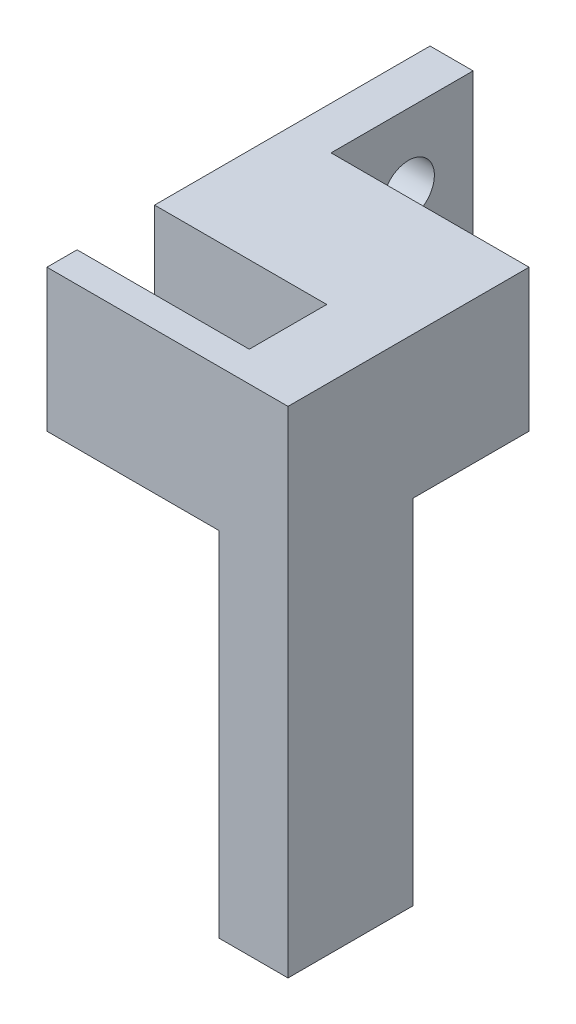
SolidWorks part; units mm, degrees
ref_plane "前视基准面" through (0, 0, 0) normal (0, 0, 1) x (1, 0, 0)
ref_plane "上视基准面" through (0, 0, 0) normal (0, 1, 0) x (1, 0, 0)
ref_plane "右视基准面" through (0, 0, 0) normal (1, 0, 0) x (0, 0, -1)
other "Configuration Table"
sketch "草图1" plane through (0, 0, 0) normal (1, 0, 0) x (0, 0, -1)
  line L5 (0, 0) -> (-2.9, 0)
  line L6 (0, 0) -> (0, -11.5)
  line L7 (0, -11.5) -> (-2.9, -11.5)
  line L8 (-2.9, 0) -> (-2.9, -11.5)
  point P4 (-0.9757, -0.6511)
  dimension "D1" = 2.9
  dimension "D2" = 11.5
extrude "凸台-拉伸1" add sketch "草图1" along normal blind 1.6 contours L7 L8 L5 L6 | L7 L8 L5 L6 region at (0, -5.75, 1.45)
sketch "草图2" plane through (0, 0, 0) normal (-1, 0, 0) x (0, 0, 1)
  line L0 (2.9, 0) -> (2.9, -11.5) construction
  line L1 (2.2, -3.3) -> (2.9, -3.3)
  line L2 (2.2, -3.3) -> (2.2, 0)
  line L3 (2.2, 0) -> (2.9, 0)
  line L4 (2.9, -3.3) -> (2.9, 0)
  line L5 (0, 0) -> (2.9, 0) construction
  line L6 (0, 0) -> (0.4, 0)
  line L7 (0, 0) -> (0, -3.3)
  line L8 (0, -3.3) -> (0.4, -3.3)
  line L9 (0.4, 0) -> (0.4, -3.3)
  point P12 (0, 0)
  dimension "D1" = 3.3
  dimension "D2" = 0.7
  dimension "D3" = 0.4
extrude "凸台-拉伸2" add sketch "草图2" along normal blind 4 contours L4 L3 L2 L1 | L9 L8 L7 L6
sketch "草图3" plane through (0, 0, 0) normal (0, 0, -1) x (-1, 0, 0)
  line L0 (-1.6, 0) -> (4, 0) construction
  line L1 (-1.6, 0) -> (4, 0)
  line L2 (-1.6, 0) -> (-1.6, -3.3)
  line L3 (-1.6, -3.3) -> (4, -3.3)
  line L4 (4, 0) -> (4, -3.3)
  line L5 (4, 0) -> (4, -3.3) construction
  line L6 (-1.6, 0) -> (-1.6, -11.5) construction
  line L7 (4, -3.3) -> (0, -3.3) construction
  point P8 (-0.613, -2.3514)
extrude "凸台-拉伸3" add sketch "草图3" along normal blind 3
sketch "草图4" plane through (0, 0, -3) normal (0, 0, -1) x (-1, 0, 0)
  line L0 (-1.6, -3.3) -> (4, -3.3) construction
  line L1 (3, -3.3) -> (4, -3.3)
  line L2 (3, -3.3) -> (3, 0)
  line L3 (3, 0) -> (4, 0)
  line L4 (4, -3.3) -> (4, 0)
  line L5 (4, -3.3) -> (4, 0) construction
  line L6 (4, 0) -> (-1.6, 0) construction
  dimension "D1" = 1
extrude "凸台-拉伸4" add sketch "草图4" along normal blind 3
sketch "草图5" plane through (-3, 0, 0) normal (1, 0, 0) x (0, 0, -1)
  line L1 (4.5, 0) -> (4.5, -3.3)
  line L2 (6, 0) -> (3, 0) construction
  line L3 (6, -3.3) -> (3, -3.3) construction
  circle A0 centre (4.5, -1.65) radius 0.6
  point P2 (0, 0)
  dimension "D1" = 1.2
extrude "切除-拉伸1" cut sketch "草图5" against normal through all contours A0
sketch "草图6" plane through (0, 0, -3) normal (0, 0, -1) x (-1, 0, 0)
  line L0 (-1.6, -3.3) -> (3, -3.3) construction
  line L1 (-1.6, -3.3) -> (3, -3.3)
  line L2 (-1.6, -3.3) -> (-1.6, 0)
  line L3 (-1.6, 0) -> (3, 0)
  line L4 (3, -3.3) -> (3, 0)
  line L5 (-1.6, -3.3) -> (-1.6, -11.5) construction
  line L6 (3, 0) -> (3, -3.3) construction
  line L7 (3, 0) -> (-1.6, 0) construction
extrude "切除-拉伸2" cut sketch "草图6" against normal blind 0.3
